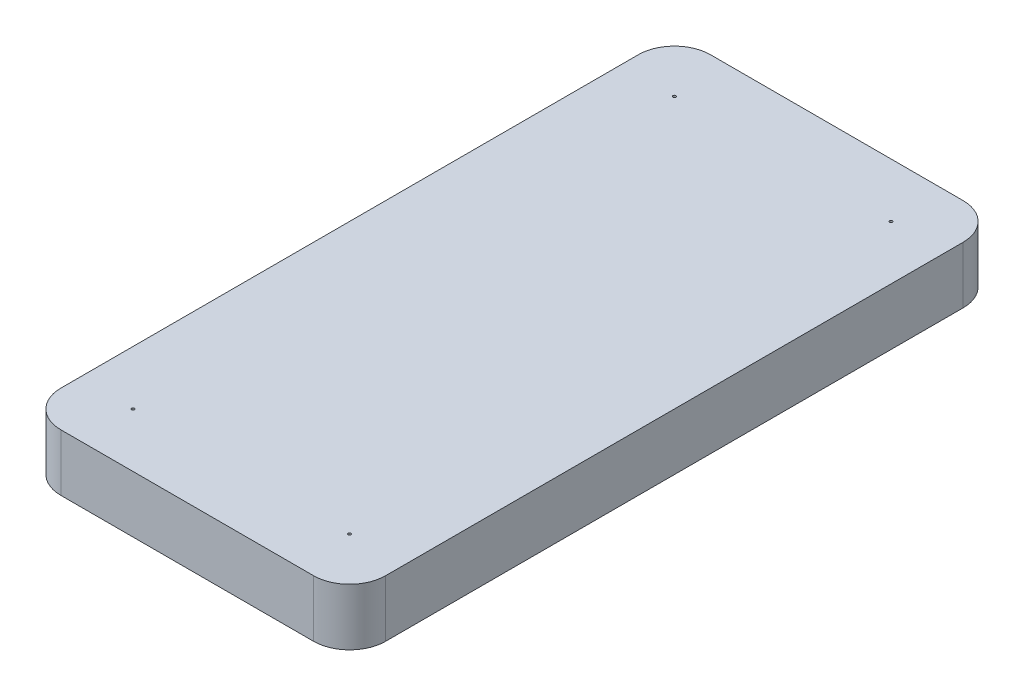
SolidWorks part; units mm, degrees
ref_plane "Front Plane" through (0, 0, 0) normal (0, 0, 1) x (1, 0, 0)
ref_plane "Top Plane" through (0, 0, 0) normal (0, 1, 0) x (1, 0, 0)
ref_plane "Right Plane" through (0, 0, 0) normal (1, 0, 0) x (0, 0, -1)
sketch "Sketch1" plane through (0, 0, 0) normal (0, 1, 0) x (1, 0, 0)
  line L1 (0, 0) -> (114.3, 0)
  line L2 (0, 0) -> (0, 228.6)
  line L3 (0, 228.6) -> (114.3, 228.6)
  line L4 (114.3, 0) -> (114.3, 228.6)
  dimension "9" = 228.6
  dimension "5.5" = 114.3
extrude "Boss-Extrude2" add sketch "Sketch1" along normal blind 20
sketch "Sketch4" plane through (0, 20, -20) normal (0, -1, 0) x (1, 0, 0)
  line L0 (114.3, -296.7063) -> (-114.3, -296.7063) construction
  line L1 (114.3, -265.75) -> (-114.3, -265.75) construction
  line L2 (114.3, -322.9) -> (-114.3, -322.9)
  line L3 (114.3, -322.9) -> (114.3, -208.6)
  line L4 (114.3, -208.6) -> (-114.3, -208.6)
  line L5 (-114.3, -322.9) -> (-114.3, -208.6)
  line L7 (0, 20) -> (114.3, 20) construction
  line L9 (0, -208.6) -> (0, 20) construction
  circle A0 centre (83.3438, -296.7063) radius 3.1
  circle A1 centre (-96.0437, -296.7063) radius 3.1
  circle A2 centre (83.3437, -234.7938) radius 3.1
  circle A3 centre (-96.0438, -234.7937) radius 3.1
  dimension "D2" = 6.2
  dimension "D3" = 30.9562
  dimension "D1" = 30.9562
  dimension "D4" = 2
sketch "Sketch5" plane through (0, 20, 0) normal (0, 1, 0) x (1, 0, 0)
  line L0 (57.15, 0) -> (57.15, 228.6) construction
  line L1 (0, 0) -> (114.3, 0) construction
  line L2 (114.3, 228.6) -> (-114.3, 228.6) construction
  line L11 (19.05, 209.55) -> (19.05, 19.05)
  line L12 (19.05, 19.05) -> (95.25, 19.05)
  line L13 (95.25, 19.05) -> (95.25, 209.55)
  line L14 (95.25, 209.55) -> (19.05, 209.55)
  line L15 (19.05, 209.55) -> (19.05, 19.05)
  line L16 (19.05, 19.05) -> (95.25, 19.05)
  line L17 (95.25, 19.05) -> (95.25, 209.55)
  line L18 (95.25, 209.55) -> (19.05, 209.55)
  circle A0 centre (95.25, 209.55) radius 0.5
  circle A1 centre (95.25, 19.05) radius 0.5
  circle A2 centre (19.05, 19.05) radius 0.5
  circle A3 centre (19.05, 209.55) radius 0.5
  dimension "D2" = 1
  dimension "D3" = 1
  dimension "D4" = 1
  dimension "D5" = 1
  dimension "D1" = 19.05
extrude "Cut-Extrude1" cut sketch "Sketch5" against normal through all contours L17 A0 L18 | L18 A0 L17 | L16 A1 L17 | L17 A1 L16 | L15 A2 L16 | L16 A2 L15 | L15 A3 L18 | L18 A3 L15 region at (19.2622, 20, -209.3378) region at (18.9793, 20, -209.6207) region at (19.2622, 20, -19.2622) region at (18.9793, 20, -18.9793) region at (95.3207, 20, -209.6207) region at (95.0378, 20, -209.3378) region at (95.0378, 20, -19.2622) region at (95.3207, 20, -18.9793)
fillet "Fillet1" radius 12.7 4 edges at (0, 10, -228.6) (114.3, 10, -228.6) (0, 10, 0) (114.3, 10, 0)
equation "\"2c\"=0.787402"
